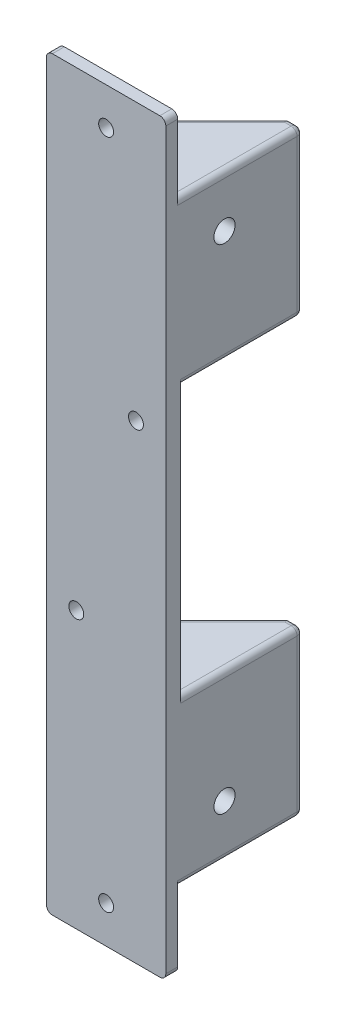
SolidWorks part; units mm, degrees
material "ABS"
ref_plane "X-Y Datum" through (0, 0, 0) normal (0, 0, 1) x (1, 0, 0)
ref_plane "X-Z Datum" through (0, 0, 0) normal (0, 1, 0) x (1, 0, 0)
ref_plane "Y-Z Datum" through (0, 0, 0) normal (1, 0, 0) x (0, 0, -1)
sketch "Sketch1" plane through (0, 0, 0) normal (0, 1, 0) x (1, 0, 0)
  line L0 (0, 0) -> (-25.4, 0)
  line L1 (-25.4, 0) -> (-25.4, 6.985)
  line L2 (-25.4, 6.985) -> (-3.175, 29.21)
  line L3 (0, 29.21) -> (0, 0)
  line L4 (-3.175, 29.21) -> (0, 29.21)
  dimension "D1" = 25.4
  dimension "D2" = 45
  dimension "D3" = 6.985
  dimension "D4" = 3.175
extrude "Boss-Extrude1" add sketch "Sketch1" along normal blind 127
ref_plane "Plane1" through (0, 63.5, 0) normal (0, -1, 0) x (-1, 0, 0)
sketch "Sketch2" plane through (0, 63.5, 0) normal (0, -1, 0) x (-1, 0, 0)
  line L0 (3.175, 3.175) -> (25.4, 3.175)
  line L2 (25.4, 3.175) -> (25.4, 6.985)
  line L3 (25.4, 6.985) -> (3.175, 29.21)
  line L4 (3.175, 29.21) -> (3.175, 3.175)
  line L5 (25.4, 6.985) -> (25.4, 0) construction
  line L8 (3.175, 29.21) -> (25.4, 6.985) construction
  line L9 (3.175, 3.175) -> (3.175, 0)
  line L10 (3.175, 29.21) -> (25.4, 6.985) construction
  line L11 (3.175, 3.175) -> (0, 3.175)
  line L12 (0, 0) -> (0, 29.21) construction
  line L13 (25.4, 0) -> (0, 0) construction
  dimension "D1" = 3.175
extrude "Cut-Extrude1" cut sketch "Sketch2" against normal offset from surface (28.575 mm away) 3.175 from offset 31.75 contours L3 L4 L0 L2 region at (-11.5291, 63.5, -12.0155) up to face at (-10.795, 127, -13.081) offset against normal yes
extrude "Cut-Extrude2" cut sketch "Sketch2<2>" along normal offset from surface (28.575 mm away) 3.175 from offset 31.75 contours L3 L4 L0 L2 region at (-11.5291, 63.5, -12.0155) up to face at (-10.795, 0, -13.081)
sketch "Sketch2<2>" plane through (0, 63.5, 0) normal (0, -1, 0) x (-1, 0, 0) same geometry as "Sketch2"
sketch "Sketch3" plane through (0, 63.5, 0) normal (0, -1, 0) x (-1, 0, 0)
  line L0 (0, 0) -> (0, 29.21) construction
  line L1 (25.4, 3.175) -> (0, 3.175)
  line L2 (25.4, 3.175) -> (25.4, 53.975)
  line L3 (25.4, 53.975) -> (0, 53.975)
  line L4 (0, 3.175) -> (0, 53.975)
  line L5 (25.4, 3.175) -> (25.4, 6.985) construction
  line L6 (25.4, 3.175) -> (3.175, 3.175) construction
  dimension "D1" = 50.8
extrude "Cut-Extrude4" cut sketch "Sketch3" against normal mid plane 57.15
sketch "Sketch6" plane through (0, 0, 0) normal (0, 0, 1) x (1, 0, 0)
  line L0 (-25.4, 63.5) -> (0, 63.5) construction
  line L1 (0, 127) -> (-25.4, 127)
  line L2 (0, 127) -> (0, 142.875)
  line L3 (0, 142.875) -> (-25.4, 142.875)
  line L4 (-25.4, 127) -> (-25.4, 142.875)
  line L5 (-25.4, 92.075) -> (-25.4, 34.925) construction
  line L7 (0, 127) -> (0, 0) construction
  line L8 (-25.4, 0) -> (-25.4, -15.875)
  line L9 (0, -15.875) -> (-25.4, -15.875)
  line L10 (0, 0) -> (0, -15.875)
  line L11 (0, 0) -> (-25.4, 0)
  circle A0 centre (-12.7, 134.9375) radius 1.5875
  circle A1 centre (-12.7, -7.9375) radius 1.5875
  point P10 (-25.4, 134.9375)
  point P13 (-12.7, 142.875)
  dimension "D1" = 3.175
  dimension "D2" = 15.875
extrude "Boss-Extrude2" add sketch "Sketch6" against normal blind 2.54
sketch "Sketch5" plane through (0, 0, -3.175) normal (0, 0, -1) x (-1, 0, 0)
  line L0 (0, 63.5) -> (25.4, 63.5) construction
  line L1 (6.35, 84.1375) -> (19.05, 84.1375) construction
  line L2 (6.35, 84.1375) -> (6.35, 42.8625) construction
  line L3 (6.35, 42.8625) -> (19.05, 42.8625) construction
  line L4 (19.05, 84.1375) -> (19.05, 42.8625) construction
  line L5 (6.35, 84.1375) -> (19.05, 42.8625) construction
  line L6 (6.35, 42.8625) -> (19.05, 84.1375) construction
  line L7 (0, 92.075) -> (0, 34.925) construction
  line L8 (25.4, 92.075) -> (25.4, 34.925) construction
  circle A0 centre (6.35, 84.1375) radius 1.5875
  circle A1 centre (19.05, 42.8625) radius 1.5875
  point P0 (12.7, 63.5)
  point P6 (12.7, 63.5)
  dimension "D3" = 3.175
  dimension "D1" = 12.7
  dimension "D2" = 41.275
extrude "Cut-Extrude6" cut sketch "Sketch5" against normal through all both and the other way through all
sketch "Sketch7" plane through (-3.175, 0, 0) normal (-1, 0, 0) x (0, 0, 1)
  line L0 (-12.4963, 11) -> (-12.4963, 116) construction
  line L1 (-13.2715, 63.5) -> (13.2715, 63.5) construction
  line L2 (-29.21, 3.175) -> (-29.21, 31.75) construction
  circle A0 centre (-12.4963, 11) radius 2.25
  circle A1 centre (-12.4963, 116) radius 2.25
  point P4 (-12.4963, 63.5)
  dimension "D2" = 4.5
  dimension "D1" = 105
  dimension "D3" = 16.7137
extrude "Cut-Extrude7" cut sketch "Sketch7" against normal through all
fillet "Fillet1" radius 1.27 31 edges at (0, 0, -15.875) (0, 34.925, -16.1925) (0, 127, -15.875) (0, 92.075, -16.1925) (-1.5875, 127, -29.21) (-25.4, 34.925, -5.08) (-14.2875, 34.925, -18.0975) (-1.5875, 34.925, -29.21) (-14.2875, 127, -18.0975) (-25.4, 127, -4.7625) (-1.5875, 92.075, -29.21) (-14.2875, 92.075, -18.0975) (-25.4, 92.075, -5.08) (-25.4, 142.875, -1.27) (-25.4, -15.875, -1.27) (0, -15.875, -1.27) (-14.2875, 0, -18.0975) (-1.5875, 0, -29.21) (-14.2875, 123.825, -3.175) (-3.175, 123.825, -16.1925) (-14.2875, 95.25, -3.175) (-3.175, 109.5375, -3.175) (-3.175, 95.25, -16.1925) (-3.175, 3.175, -16.1925) (-14.2875, 3.175, -3.175) (-14.2875, 31.75, -3.175) (-3.175, 17.4625, -3.175) (-3.175, 31.75, -16.1925) (0, 17.4625, -29.21) (0, 109.5375, -29.21) (0, 142.875, -1.27)
